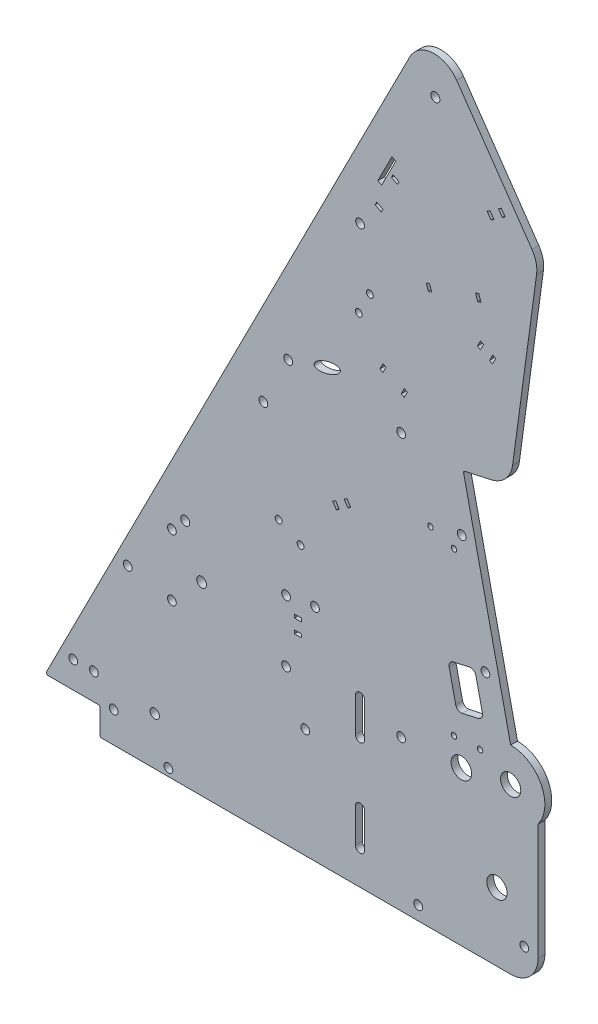
SolidWorks part; units mm, degrees
other "Markup1"
sketch "Sketch5"
ref_plane "Front Plane" through (0, 0, 0) normal (0, 0, 1) x (1, 0, 0)
ref_plane "Top Plane" through (0, 0, 0) normal (0, 1, 0) x (1, 0, 0)
ref_plane "Right Plane" through (0, 0, 0) normal (1, 0, 0) x (0, 0, -1)
sketch "Sketch1" plane through (0, 0, 0) normal (0, 0, 1) x (1, 0, 0)
  line L1 (228.6, -12.7) -> (228.6, 53.975)
  line L2 (178.7547, 351.4131) -> (0, 0)
  line L3 (228.6, 279.4) -> (178.7547, 351.4131)
  line L5 (0, 0) -> (25.4, 0)
  line L6 (25.4, 0) -> (25.4, -12.7)
  line L7 (25.4, -12.7) -> (228.6, -12.7)
  line L9 (215.9, 79.375) -> (193.9097, 178.5667)
  line L10 (193.9097, 178.5667) -> (215.6079, 183.377)
  line L11 (215.6079, 183.377) -> (228.6, 279.4)
  arc A0 (228.6, 53.975) -> (215.9, 79.375) centre (215.9, 63.5) ccw
  dimension "D7" = 12.7
  dimension "D8" = 76.2
  dimension "D10" = 31.75
  dimension "D2" = 292.1
  dimension "D3" = 25.4
  dimension "D4" = 215.9
  dimension "D5" = 394.2644
  dimension "D6" = 203.2
  dimension "D9" = 63.039
  dimension "D11" = 101.6
  dimension "D12" = 12.5
  dimension "D13" = 22.225
extrude "Boss-Extrude1" add sketch "Sketch1" along normal blind 3.175
sketch "Sketch2" plane through (0, 0, 3.175) normal (0, 0, 1) x (1, 0, 0)
  line L0 (178.7547, 351.4131) -> (0, 0) construction
  line L1 (25.4, -12.7) -> (228.6, -12.7) construction
  line L2 (215.9, 79.375) -> (193.9097, 178.5667) construction
  line L3 (193.9097, 178.5667) -> (215.6079, 183.377) construction
  line L4 (215.9, 79.375) -> (193.9097, 178.5667) construction
  line L5 (64.9432, 94.0578) -> (72.5445, 73.1732) construction
  line L6 (64.9432, 94.0578) -> (103.3734, 94.0578) construction
  line L10 (228.6, -12.7) -> (228.6, 53.975) construction
  circle A0 centre (64.9432, 94.0578) radius 2.0955
  circle A1 centre (180.975, 322.1643) radius 2.0955
  circle A2 centre (72.5445, 73.1732) radius 2.286
  circle A3 centre (193.2078, 152.3944) radius 2.032
  circle A4 centre (215.9, 63.5) radius 4.699
  circle A7 centre (173.0375, -6.35) radius 2.032
  circle A8 centre (204.203, 102.7985) radius 2.032
  circle A26 centre (209.55, 19.05) radius 4.699
  arc A30 (228.6, 53.975) -> (215.9, 79.375) centre (215.9, 63.5) ccw construction
  circle A31 centre (165.1, 179.3875) radius 2.032
  circle A35 centre (111.724, 87.4607) radius 2.032
  circle A36 centre (111.724, 58.8857) radius 2.032
  circle A37 centre (58.765, 58.8857) radius 2.032
  circle A38 centre (58.765, 87.4607) radius 2.032
  circle A39 centre (111.724, 58.8857) radius 1.905 construction
  circle A42 centre (111.724, 87.4607) radius 1.905 construction
  circle A43 centre (58.765, 58.8857) radius 1.905 construction
  circle A44 centre (58.765, 87.4607) radius 1.905 construction
  dimension "D3" = 4.191
  dimension "D5" = 4.191
  dimension "D9" = 4.572
  dimension "D20" = 9.398
  dimension "D23" = 9.398
  dimension "D18" = 4.064
  dimension "D26" = 4.064
  dimension "D14" = 4.064
  dimension "D10" = 4.064
  dimension "D2" = 15.24
  dimension "D6" = 15.24
  dimension "D7" = 22.225
  dimension "D21" = 44.45
  dimension "D22" = 6.35
  dimension "D19" = 160.3375
  dimension "D24" = 44.45
  dimension "D25" = 6.35
  dimension "D27" = 25.4
  dimension "D28" = 50.8
  dimension "D29" = 6.35
  dimension "D17" = 6.35
  dimension "D33" = 55.5625
  dimension "D15" = 114.3
  dimension "D4" = 180.975
  dimension "D8" = 70
extrude "Cut-Extrude1" cut sketch "Sketch2" against normal through all
sketch "Sketch7" plane through (0, 0, 3.175) normal (0, 0, 1) x (1, 0, 0)
  line L0 (146.05, 3.175) -> (146.05, 19.05) construction
  line L1 (143.891, 3.175) -> (143.891, 19.05)
  line L2 (148.209, 3.175) -> (148.209, 19.05)
  line L3 (146.05, 47.625) -> (146.05, 63.5) construction
  line L4 (143.891, 47.625) -> (143.891, 63.5)
  line L5 (148.209, 47.625) -> (148.209, 63.5)
  line L6 (25.4, -12.7) -> (228.6, -12.7) construction
  line L12 (228.6, -12.7) -> (228.6, 53.975) construction
  line L13 (25.4, -12.7) -> (228.6, -12.7) construction
  arc A0 (143.891, 3.175) -> (148.209, 3.175) centre (146.05, 3.175) ccw
  arc A1 (148.209, 19.05) -> (143.891, 19.05) centre (146.05, 19.05) ccw
  arc A2 (143.891, 47.625) -> (148.209, 47.625) centre (146.05, 47.625) ccw
  arc A3 (148.209, 63.5) -> (143.891, 63.5) centre (146.05, 63.5) ccw
  circle A8 centre (50.8, 9.525) radius 2.159
  point P2 (146.05, 11.1125)
  point P9 (146.05, 55.5625)
  dimension "D1" = 4.318
  dimension "D5" = 4.318
  dimension "D2" = 15.875
  dimension "D3" = 15.875
  dimension "D4" = 44.45
  dimension "D6" = 95.25
  dimension "D7" = 82.55
  dimension "D8" = 15.875
  dimension "D9" = 22.225
extrude "Cut-Extrude2" cut sketch "Sketch7" against normal through all
sketch "Sketch10" plane through (0, 0, 3.175) normal (0, 0, 1) x (1, 0, 0)
  circle A0 centre (120.65, 38.1) radius 2.032
  circle A1 centre (165.1, 57.15) radius 2.032
  circle A2 centre (13.0465, 12.3347) radius 2.032
  circle A3 centre (22.5715, 12.3347) radius 2.032
  circle A4 centre (38.2611, 62.6146) radius 2.032
  circle A5 centre (13.0465, 12.3347) radius 2.032 construction
  circle A6 centre (22.5715, 12.3347) radius 2.032 construction
  dimension "D1" = 4.064
  dimension "D3" = 38.1
  dimension "D2" = 120.65
  dimension "D4" = 63.5
  dimension "D5" = 69.85
extrude "Cut-Extrude3" cut sketch "Sketch10" against normal up to next
fillet "Fillet1" radius 12.7 4 edges at (228.6, -12.7, 1.5875) (178.7547, 351.4131, 1.5875) (215.6079, 183.377, 1.5875) (228.6, 279.4, 1.5875)
fillet "Fillet2" radius 0.7937 4 edges at (25.4, -12.7, 1.5875) (25.4, 0, 1.5875) (193.9097, 178.5667, 1.5875) (0, 0, 1.5875)
sketch "Sketch12" plane through (0, 0, 3.175) normal (0, 0, 1) x (1, 0, 0)
  circle A0 centre (31.75, 1.5875) radius 2.032
  circle A1 centre (173.0375, -6.35) radius 2.032
  circle A2 centre (222.25, 1.5875) radius 2.032
  circle A3 centre (57.15, -9.2075) radius 2.032
  circle A4 centre (57.15, -9.2075) radius 2.286 construction
  dimension "D1" = 4.064
  dimension "D2" = 4.064
extrude "Cut-Extrude5" cut sketch "Sketch12" against normal through all
sketch "Sketch13" plane through (0, 0, 3.175) normal (0, 0, 1) x (1, 0, 0)
  line L1 (228.6, 0) -> (228.6, 53.975) construction
  line L2 (1.2943, 0) -> (24.6062, 0) construction
  line L3 (26.1937, -12.7) -> (215.9, -12.7) construction
  line L8 (178.2697, 245.9923) -> (176.7582, 245.5069)
  line L9 (179.2404, 242.9693) -> (178.2697, 245.9923)
  line L10 (177.7289, 242.4839) -> (179.2404, 242.9693)
  line L11 (176.7582, 245.5069) -> (177.7289, 242.4839)
  line L12 (178.2697, 245.9923) -> (176.7582, 245.5069)
  line L13 (179.2404, 242.9693) -> (178.2697, 245.9923)
  line L14 (177.7289, 242.4839) -> (179.2404, 242.9693)
  line L15 (176.7582, 245.5069) -> (177.7289, 242.4839)
  line L16 (160.8477, 288.1984) -> (154.2836, 275.294)
  line L17 (200.6096, 249.8308) -> (202.1211, 250.3161)
  line L18 (199.639, 252.8538) -> (200.6096, 249.8308)
  line L19 (201.1505, 253.3391) -> (199.639, 252.8538)
  line L20 (202.1211, 250.3161) -> (201.1505, 253.3391)
  line L21 (200.6096, 249.8308) -> (202.1211, 250.3161)
  line L22 (199.639, 252.8538) -> (200.6096, 249.8308)
  line L23 (201.1505, 253.3391) -> (199.639, 252.8538)
  line L24 (202.1211, 250.3161) -> (201.1505, 253.3391)
  line L25 (160.8477, 288.1984) -> (162.6303, 287.2917)
  line L26 (160.5905, 279.7801) -> (163.4204, 278.3406)
  line L27 (161.3102, 281.1951) -> (160.5905, 279.7801)
  line L28 (164.1402, 279.7556) -> (161.3102, 281.1951)
  line L29 (163.4204, 278.3406) -> (164.1402, 279.7556)
  line L30 (160.5905, 279.7801) -> (163.4204, 278.3406)
  line L31 (161.3102, 281.1951) -> (160.5905, 279.7801)
  line L32 (164.1402, 279.7556) -> (161.3102, 281.1951)
  line L33 (163.4204, 278.3406) -> (164.1402, 279.7556)
  line L34 (154.2836, 275.294) -> (156.0662, 274.3872)
  line L35 (162.6303, 287.2917) -> (156.0662, 274.3872)
  line L36 (153.7897, 266.4104) -> (153.0699, 264.9954)
  line L37 (156.6196, 264.9709) -> (153.7897, 266.4104)
  line L38 (155.8998, 263.5559) -> (156.6196, 264.9709)
  line L39 (153.0699, 264.9954) -> (155.8998, 263.5559)
  line L40 (153.7897, 266.4104) -> (153.0699, 264.9954)
  line L41 (156.6196, 264.9709) -> (153.7897, 266.4104)
  line L42 (155.8998, 263.5559) -> (156.6196, 264.9709)
  line L43 (153.0699, 264.9954) -> (155.8998, 263.5559)
  line L110 (153.9925, 274.7218) -> (157.3929, 281.4066) construction
  line L111 (155.7751, 273.815) -> (159.1755, 280.4999) construction
  line L122 (203.3303, 234.0299) -> (201.9154, 234.7497)
  line L123 (201.8908, 231.2) -> (203.3303, 234.0299)
  line L124 (200.4759, 231.9198) -> (201.8908, 231.2)
  line L125 (201.9154, 234.7497) -> (200.4759, 231.9198)
  line L126 (203.3303, 234.0299) -> (201.9154, 234.7497)
  line L127 (201.8908, 231.2) -> (203.3303, 234.0299)
  line L128 (200.4759, 231.9198) -> (201.8908, 231.2)
  line L129 (201.9154, 234.7497) -> (200.4759, 231.9198)
  line L130 (206.1357, 229.0407) -> (207.5507, 228.321)
  line L131 (207.5752, 231.8707) -> (206.1357, 229.0407)
  line L132 (208.9902, 231.1509) -> (207.5752, 231.8707)
  line L133 (207.5507, 228.321) -> (208.9902, 231.1509)
  line L134 (206.1357, 229.0407) -> (207.5507, 228.321)
  line L135 (207.5752, 231.8707) -> (206.1357, 229.0407)
  line L136 (208.9902, 231.1509) -> (207.5752, 231.8707)
  line L137 (207.5507, 228.321) -> (208.9902, 231.1509)
  line L138 (211.5405, 292.889) -> (210.2352, 291.9855)
  line L139 (213.3475, 290.2784) -> (211.5405, 292.889)
  line L140 (212.0422, 289.3749) -> (213.3475, 290.2784)
  line L141 (210.2352, 291.9855) -> (212.0422, 289.3749)
  line L142 (211.5405, 292.889) -> (210.2352, 291.9855)
  line L143 (213.3475, 290.2784) -> (211.5405, 292.889)
  line L144 (212.0422, 289.3749) -> (213.3475, 290.2784)
  line L145 (210.2352, 291.9855) -> (212.0422, 289.3749)
  line L146 (206.3193, 289.275) -> (205.014, 288.3715)
  line L147 (208.1263, 286.6644) -> (206.3193, 289.275)
  line L148 (206.821, 285.7609) -> (208.1263, 286.6644)
  line L149 (205.014, 288.3715) -> (206.821, 285.7609)
  line L150 (206.3193, 289.275) -> (205.014, 288.3715)
  line L151 (208.1263, 286.6644) -> (206.3193, 289.275)
  line L152 (206.821, 285.7609) -> (208.1263, 286.6644)
  line L153 (205.014, 288.3715) -> (206.821, 285.7609)
  line L184 (133.3504, 136.102) -> (135.0815, 133.4404)
  line L185 (133.3504, 136.102) -> (134.6812, 136.9675)
  line L186 (135.0815, 133.4404) -> (136.4123, 134.3059)
  line L187 (155.2281, 200.1197) -> (156.643, 199.3999)
  line L188 (156.6676, 202.9496) -> (155.2281, 200.1197)
  line L189 (158.0826, 202.2298) -> (156.6676, 202.9496)
  line L190 (156.643, 199.3999) -> (158.0826, 202.2298)
  line L191 (155.2281, 200.1197) -> (156.643, 199.3999)
  line L192 (156.6676, 202.9496) -> (155.2281, 200.1197)
  line L193 (158.0826, 202.2298) -> (156.6676, 202.9496)
  line L194 (156.643, 199.3999) -> (158.0826, 202.2298)
  line L195 (134.6812, 136.9675) -> (136.4123, 134.3059)
  line L196 (165.1328, 195.0814) -> (166.5478, 194.3617)
  line L197 (166.5723, 197.9113) -> (165.1328, 195.0814)
  line L198 (167.9873, 197.1916) -> (166.5723, 197.9113)
  line L199 (166.5478, 194.3617) -> (167.9873, 197.1916)
  line L200 (165.1328, 195.0814) -> (166.5478, 194.3617)
  line L201 (166.5723, 197.9113) -> (165.1328, 195.0814)
  line L202 (167.9873, 197.1916) -> (166.5723, 197.9113)
  line L203 (166.5478, 194.3617) -> (167.9873, 197.1916)
  line L204 (140.4047, 136.9025) -> (138.6737, 139.5641)
  line L205 (140.4047, 136.9025) -> (141.7355, 137.768)
  line L206 (138.6737, 139.5641) -> (140.0045, 140.4296)
  line L207 (141.7355, 137.768) -> (140.0045, 140.4296)
  line L209 (169.1053, 332.4434) -> (0.5868, 1.1536) construction
  line L210 (88.0466, 102.1523) -> (85.2167, 103.5918) construction
  line L288 (115.661, 81.8727) -> (118.836, 81.8727)
  line L289 (115.661, 81.8727) -> (115.661, 80.2852)
  line L290 (118.836, 81.8727) -> (118.836, 80.2852)
  line L291 (115.661, 80.2852) -> (118.836, 80.2852)
  line L292 (115.661, 75.5227) -> (118.836, 75.5227)
  line L293 (115.661, 75.5227) -> (115.661, 73.9352)
  line L294 (118.836, 75.5227) -> (118.836, 73.9352)
  line L295 (115.661, 73.9352) -> (118.836, 73.9352)
  line L297 (115.661, 86.2542) -> (115.661, 60.0922) construction
  line L298 (59.9715, 91.3977) -> (110.5175, 91.3977) construction
  circle A0 centre (112.7125, 182.5625) radius 2.032
  circle A1 centre (146.05, 254) radius 2.032
  circle A2 centre (101.1964, 159.9231) radius 2.032 construction
  circle A3 centre (101.1964, 159.9231) radius 2.032
  circle A4 centre (145.4254, 217.7376) radius 1.6 construction
  circle A5 centre (150.594, 227.8985) radius 1.6 construction
  circle A7 centre (145.4254, 217.7376) radius 1.6
  circle A8 centre (150.594, 227.8985) radius 1.6
  circle A9 centre (108.294, 116.1502) radius 1.6 construction
  circle A10 centre (118.455, 110.9816) radius 1.6 construction
  circle A11 centre (108.294, 116.1502) radius 1.6
  circle A12 centre (118.455, 110.9816) radius 1.6
  ellipse E0 centre (130.8261, 188.4615) end of major axis (136.864, 190.4279) minor radius 2.3812 construction
  ellipse E1 centre (130.8261, 188.4615) end of major axis (136.864, 190.4279) minor radius 2.3812
  dimension "D2" = 4.064
  dimension "D5" = 4.064
  dimension "D1" = 195.2625
  dimension "D3" = 82.55
  dimension "D4" = 254
  dimension "D6" = 115.8875
  dimension "D11" = 7.62
  dimension "D12" = 6.858
  dimension "D13" = 1.5875
  dimension "D14" = 3.175
  dimension "D15" = 4.7625
  dimension "D16" = 60
  dimension "D17" = 57.15
  dimension "D24" = 50.8
  dimension "D29" = 3.175
  dimension "D30" = 1.5875
  dimension "D31" = 4.7625
  dimension "D32" = 0
  dimension "D33" = 9.525
  dimension "D7" = 0
  dimension "D8" = 0
  dimension "D9" = 0
  dimension "D10" = 0
  dimension "D18" = 0
  dimension "D19" = 0
  dimension "D20" = 0
  dimension "D21" = 0
  dimension "D22" = 0
  dimension "D23" = 0
extrude "Cut-Extrude6" cut sketch "Sketch13" against normal through all
sketch "Sketch14" plane through (0, 0, 3.175) normal (0, 0, 1) x (1, 0, 0)
  line L5 (186.8444, 98.9502) -> (199.2434, 101.699)
  line L6 (186.8444, 98.9502) -> (190.9676, 80.3518)
  line L7 (190.9676, 80.3518) -> (203.3665, 83.1006)
  line L8 (199.2434, 101.699) -> (203.3665, 83.1006)
  line L14 (202.8168, 85.5804) -> (199.7931, 99.2192) construction
  line L15 (193.4474, 80.9015) -> (200.8868, 82.5508) construction
  line L16 (187.3942, 96.4704) -> (190.4178, 82.8316) construction
  line L17 (196.7636, 101.1493) -> (189.3242, 99.5) construction
  circle A0 centre (189.6022, 69.9806) radius 1.27
  circle A1 centre (201.7089, 70.5092) radius 1.27
  circle A2 centre (189.6022, 69.9806) radius 1.27 construction
  circle A3 centre (201.7089, 70.5092) radius 1.27 construction
  circle A4 centre (165.1, 57.15) radius 2.032
  circle A5 centre (125.1498, 89.5229) radius 2.032
  circle A6 centre (178.7216, 148.5324) radius 1.27
  circle A8 centre (178.7216, 148.5324) radius 1.27 construction
  circle A9 centre (189.6226, 145.0954) radius 1.27
  circle A10 centre (189.6226, 145.0954) radius 1.27 construction
  point P8 (152.4, 88.9)
  dimension "D1" = 4.064
extrude "Cut-Extrude7" cut sketch "Sketch14" against normal through all both and the other way through all
fillet "Fillet3" radius 2.54 4 edges at (199.2434, 101.699, 1.5875) (186.8444, 98.9502, 1.5875) (190.9676, 80.3518, 1.5875) (203.3665, 83.1006, 1.5875)
sketch "Sketch15" plane through (0, 0, 3.175) normal (0, 0, 1) x (1, 0, 0)
  circle A0 centre (193.04, 58.801) radius 4.7625 construction
  circle A1 centre (193.04, 58.801) radius 4.7625
extrude "Cut-Extrude8" cut sketch "Sketch15" against normal through all
equation "\"D6@Sketch2\"=\"D2@Sketch2\""
